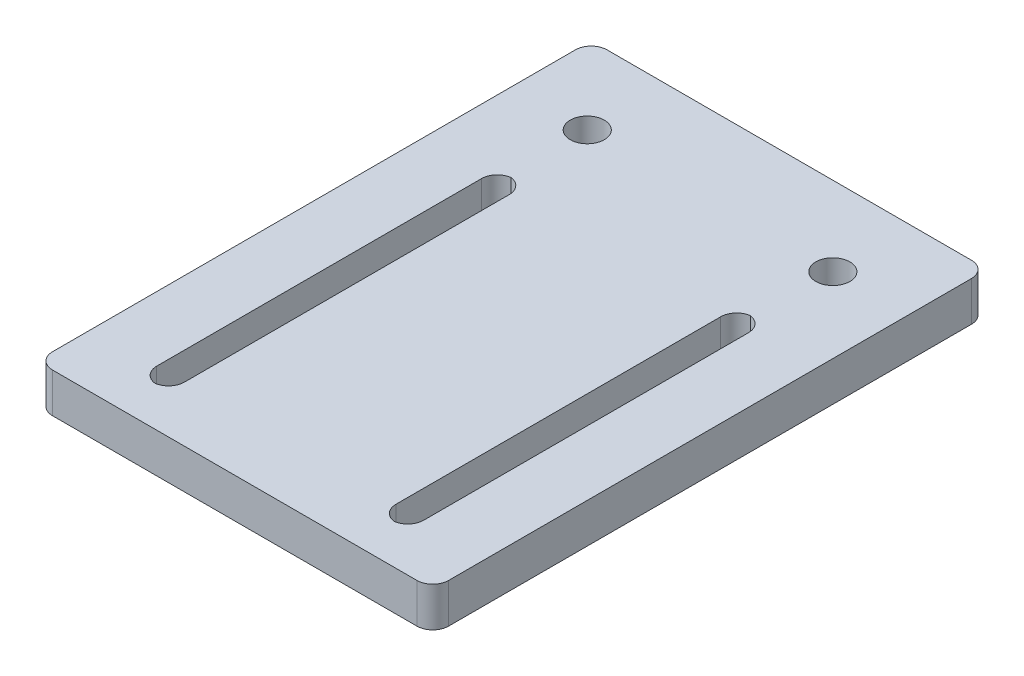
SolidWorks part; units mm, degrees
ref_plane "前基準面" through (0, 0, 0) normal (0, 0, 1) x (1, 0, 0)
ref_plane "上基準面" through (0, 0, 0) normal (0, 1, 0) x (1, 0, 0)
ref_plane "右基準面" through (0, 0, 0) normal (1, 0, 0) x (0, 0, -1)
sketch "草圖1" plane through (0, 0, 0) normal (0, 1, 0) x (1, 0, 0)
  line L0 (-23.619, 25) -> (30.175, 25) construction
  line L1 (-25, 35) -> (25, 35)
  line L2 (-25, 35) -> (-25, -35)
  line L3 (-25, -35) -> (25, -35)
  line L4 (25, 35) -> (25, -35)
  line L5 (-25, 35) -> (25, -35) construction
  line L6 (-25, -35) -> (25, 35) construction
  line L7 (0, 35) -> (0, 9.8155) construction
  line L8 (-22.5153, 15) -> (22.1797, 15) construction
  line L9 (13.35, 15) -> (16.85, -30) construction
  line L10 (-13.35, -30) -> (-16.85, -30)
  line L11 (-13.35, -30) -> (-13.35, 15)
  line L12 (-13.35, 15) -> (-16.85, 15)
  line L13 (-16.85, -30) -> (-16.85, 15)
  line L14 (-13.35, -30) -> (-16.85, 15) construction
  line L15 (-13.35, 15) -> (-16.85, -30) construction
  line L16 (13.35, -30) -> (16.85, 15) construction
  line L17 (16.85, -30) -> (16.85, 15)
  line L18 (13.35, 15) -> (16.85, 15)
  line L19 (13.35, -30) -> (13.35, 15)
  line L20 (13.35, -30) -> (16.85, -30)
  circle A0 centre (-15.5, 25) radius 2.15
  circle A1 centre (15.5, 25) radius 2.15
  point P0 (0, 0)
  point P16 (-15.1, -7.5)
  point P25 (15.1, -7.5)
  dimension "D5" = 4.3
  dimension "D1" = 70
  dimension "D2" = 50
  dimension "D3" = 10
  dimension "D4" = 15.5
  dimension "D6" = 10
  dimension "D7" = 45
  dimension "D8" = 3.5
extrude "填料-伸長1" add sketch "草圖1" along normal blind 5
fillet "圓角1" radius 2 8 edges at (16.85, 2.5, 30) (-13.35, 2.5, 30) (13.35, 2.5, 30) (-16.85, 2.5, 30) (16.85, 2.5, -15) (13.35, 2.5, -15) (-13.35, 2.5, -15) (-16.85, 2.5, -15)
fillet "圓角2" radius 2 4 edges at (-25, 2.5, -35) (25, 2.5, -35) (25, 2.5, 35) (-25, 2.5, 35)
